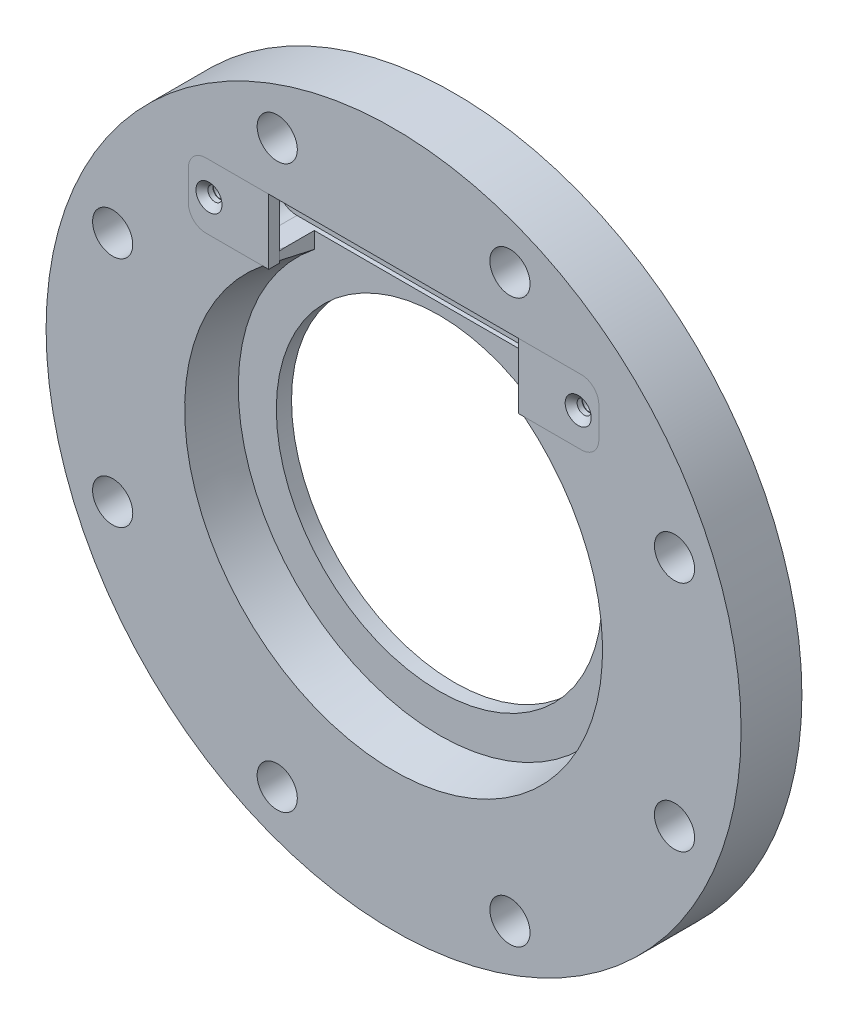
SolidWorks part; units mm, degrees
ref_plane "Front Plane" through (0, 0, 0) normal (0, 0, 1) x (1, 0, 0)
ref_plane "Top Plane" through (0, 0, 0) normal (0, 1, 0) x (1, 0, 0)
ref_plane "Right Plane" through (0, 0, 0) normal (1, 0, 0) x (0, 0, -1)
sketch "Sketch1" plane through (0, 0, 0) normal (0, 0, 1) x (1, 0, 0)
  line L0 (0, 0) -> (-53.5757, 129.3431) construction
  line L1 (0, 0) -> (0, 140) construction
  circle A1 centre (0, 0) radius 160
  circle A2 centre (0, 0) radius 75
  circle A3 centre (0, 0) radius 140 construction
  circle A4 centre (-53.5757, 129.3431) radius 9.25
  circle A5 centre (53.5757, 129.3431) radius 9.25
  circle A6 centre (129.3431, 53.5757) radius 9.25
  circle A7 centre (129.3431, -53.5757) radius 9.25
  circle A8 centre (53.5757, -129.3431) radius 9.25
  circle A9 centre (-53.5757, -129.3431) radius 9.25
  circle A10 centre (-129.3431, -53.5757) radius 9.25
  circle A11 centre (-129.3431, 53.5757) radius 9.25
  dimension "D1" = 150
  dimension "D2" = 320
  dimension "D3" = 280
  dimension "D4" = 18.5
  dimension "D5" = 22.5
  dimension "D6" = 8
extrude "Boss-Extrude1" add sketch "Sketch1" along normal mid plane 28
sketch "Sketch2" plane through (0, 0, 14) normal (0, 0, 1) x (1, 0, 0)
  circle A0 centre (0, 0) radius 92.5
  circle A3 centre (0, 0) radius 75 construction
  dimension "D1" = 17.5
extrude "Cut-Extrude1" cut sketch "Sketch2" against normal blind 21
sketch "Sketch14" plane through (0, 0, -7) normal (0, 0, 1) x (1, 0, 0)
  circle A1 centre (0, 0) radius 92.5
  circle A2 centre (0, 0) radius 92.5
  dimension "D1" = 0
extrude "Cut-Extrude3" cut sketch "Sketch14" along normal blind 50 draft 10 draft outward yes
sketch "Sketch3" plane through (0, 0, 0) normal (0, 0, 1) x (1, 0, 0)
  line L0 (0, 75) -> (0, 90) construction
  line L1 (-77.5, 80) -> (77.5, 80)
  line L2 (-77.5, 80) -> (-77.5, 100)
  line L3 (-77.5, 100) -> (77.5, 100)
  line L4 (77.5, 80) -> (77.5, 100)
  line L5 (-77.5, 80) -> (77.5, 100) construction
  line L6 (-77.5, 100) -> (77.5, 80) construction
  circle A0 centre (0, 0) radius 75 construction
  point P0 (0, 90)
  dimension "D3" = 155
  dimension "D1" = 20
  dimension "D2" = 15
extrude "Cut-Extrude2" cut sketch "Sketch3" against normal blind 9 and the other way blind 50
fillet "Fillet1" radius 2 2 edges
sketch "Sketch18" plane through (0, 0, 14) normal (0, 0, 1) x (1, 0, 0)
  line L0 (-77.5, 100) -> (-77.5, 80) construction
  line L1 (-86.5, 75) -> (-57.5, 75)
  line L2 (-94.5, 83) -> (-94.5, 97)
  line L3 (-86.5, 105) -> (-57.5, 105)
  line L4 (-57.5, 75) -> (-57.5, 105)
  line L5 (-77.5, 90) -> (-69.6835, 90) construction
  line L7 (0, 100) -> (0, 73.7925) construction
  line L8 (-77.5, 100) -> (77.5, 100) construction
  line L9 (86.5, 105) -> (57.5, 105)
  line L10 (57.5, 75) -> (57.5, 105)
  line L11 (86.5, 75) -> (57.5, 75)
  line L12 (94.5, 83) -> (94.5, 97)
  arc A0 (-86.5, 75) -> (-94.5, 83) centre (-86.5, 83) cw
  arc A1 (-94.5, 97) -> (-86.5, 105) centre (-86.5, 97) cw
  arc A2 (86.5, 75) -> (94.5, 83) centre (86.5, 83) ccw
  arc A3 (94.5, 97) -> (86.5, 105) centre (86.5, 97) ccw
  point P0 (-77.5, 90)
  dimension "D3" = 8
  dimension "D1" = 17
  dimension "D2" = 30
  dimension "D4" = 20
extrude "Cut-Extrude4" cut sketch "Sketch18" against normal blind 5
sketch "Sketch19" plane through (0, 0, 9) normal (0, 0, 1) x (1, 0, 0)
  line L0 (-77.5, 80) -> (-77.5, 100) construction
  line L1 (-85, 90) -> (-77.5, 90) construction
  line L2 (0, 0) -> (0, 145.6527) construction
  circle A0 centre (-85, 90) radius 3
  circle A1 centre (85, 90) radius 3
  dimension "D1" = 170
  dimension "D2" = 6
extrude "Cut-Extrude5" cut sketch "Sketch19" against normal blind 20
chamfer "Chamfer1" distance 3 angle 45 2 edges at (82, 90, -11) (-82, 90, -11)
fillet "Fillet2" radius 10 4 edges at (-77.5, 80, 0) (-77.5, 100, 0) (77.5, 80, 0) (77.5, 100, 0)
sketch "Sketch20" plane through (0, 0, 9) normal (0, 0, 1) x (1, 0, 0)
  line L0 (57.5, 105) -> (57.5, 100) construction
  line L1 (-57.5, 87.3852) -> (-35.6506, 87.3852)
  line L2 (-57.5, 87.3852) -> (-57.5, 69.7044)
  line L3 (-57.5, 69.7044) -> (-35.6506, 69.7044)
  line L4 (-35.6506, 87.3852) -> (-35.6506, 69.7044)
  line L5 (35.6506, 87.3852) -> (57.5, 87.3852)
  line L6 (35.6506, 87.3852) -> (35.6506, 69.7044)
  line L7 (35.6506, 69.7044) -> (57.5, 69.7044)
  line L8 (57.5, 87.3852) -> (57.5, 69.7044)
  line L9 (-57.5, 100) -> (-57.5, 105) construction
  line L10 (0, 0) -> (0, 223.6063) construction
  line L11 (-86.5, 75) -> (-60.2494, 75) construction
  dimension "D1" = 17.6808
  dimension "D2" = 21.8494
  dimension "D3" = 5.2956
extrude "Cut-Extrude6" cut sketch "Sketch20" against normal up to surface (16 mm away) and the other way blind 160 up to face at (75, 0, -7)
sketch "Sketch22" plane through (0, 0, 9) normal (0, 0, 1) x (1, 0, 0)
  line L5 (-57.5, 105) -> (-86.5, 105) construction
  line L6 (-94.5, 97) -> (-94.5, 83) construction
  line L7 (-57.5, 105) -> (-86.5, 105)
  line L8 (-94.5, 97) -> (-94.5, 83)
  line L9 (-57.5, 105) -> (-57.5, 75)
  line L10 (-86.5, 75) -> (-57.5, 75)
  arc A0 (-94.5, 83) -> (-86.5, 75) centre (-86.5, 83) ccw construction
  arc A1 (-86.5, 105) -> (-94.5, 97) centre (-86.5, 97) ccw construction
  arc A2 (-94.5, 83) -> (-86.5, 75) centre (-86.5, 83) ccw
  arc A3 (-86.5, 105) -> (-94.5, 97) centre (-86.5, 97) ccw
  circle A4 centre (-85, 90) radius 3.25
  dimension "D1" = 6.5
extrude "Boss-Extrude2" add sketch "Sketch22" along normal blind 5 separate body
sketch "Sketch23" plane through (0, 0, 14) normal (0, 0, 1) x (1, 0, 0)
  circle A0 centre (-85, 90) radius 6
  dimension "D1" = 12
extrude "Cut-Extrude7" cut sketch "Sketch23" against normal blind 5 draft 45
mirror "Mirror1" about plane through (0, 0, 0) normal (1, 0, 0) of bodies 125
ref_plane "Plane1" through (0, 90, 0) normal (0, 1, 0) x (1, 0, 0)
ref_plane "Plane2" through (0, 0, 0) normal (0, 0, 1) x (1, 0, 0)
ref_axis "Axis1" through (85.081, 90, 0) along (-1, 0, 0)
sketch "Sketch24" plane through (0, 0, 14) normal (0, 0, 1) x (1, 0, 0)
  line L1 (-57.5, 105) -> (57.5, 105)
  line L2 (-57.5, 105) -> (-57.5, 100)
  line L3 (-57.5, 100) -> (57.5, 100)
  line L4 (57.5, 105) -> (57.5, 100)
extrude "Cut-Extrude8" cut sketch "Sketch24" against normal blind 5
delete or keep bodies "Body-Delete/Keep 1" [suppressed] type delete bodies bodies 125 126
delete or keep bodies "Body-Delete/Keep 2" [suppressed] type delete bodies bodies 125 126
sketch "Sketch25" plane through (0, 0, 0) normal (1, 0, 0) x (0, 0, -1)
  line L0 (-9, 90) -> (9, 90) construction
  line L1 (8, 90) -> (8, 94.6476) construction
  circle A0 centre (0, 90) radius 8
  dimension "D1" = 16
  dimension "D2" = 1
